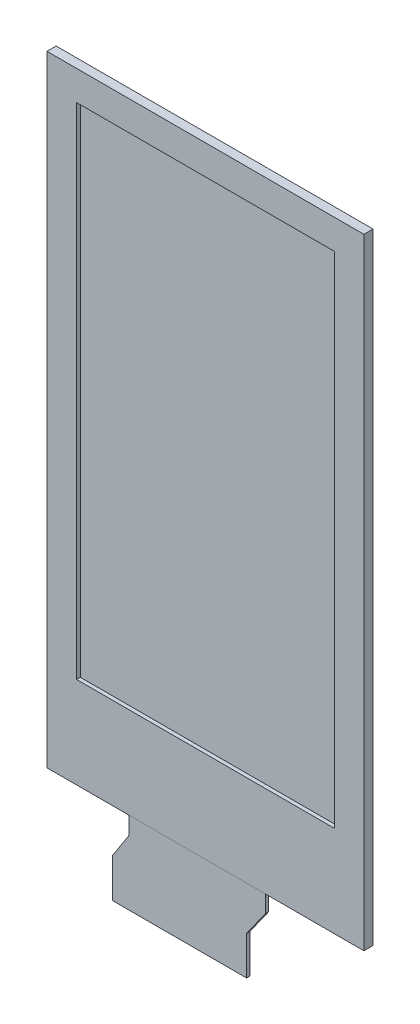
SolidWorks part; units mm, degrees
ref_plane "Front Plane" through (0, 0, 0) normal (0, 0, 1) x (1, 0, 0)
ref_plane "Top Plane" through (0, 0, 0) normal (0, 1, 0) x (1, 0, 0)
ref_plane "Right Plane" through (0, 0, 0) normal (1, 0, 0) x (0, 0, -1)
sketch "main_features_sketch" plane through (0, 0, 0) normal (0, 0, 1) x (1, 0, 0)
  line L0 (-7.152, -31.75) -> (-7.152, -33.4061)
  line L1 (12, 23.25) -> (-12, 23.25)
  line L2 (12, 23.25) -> (12, -23.25)
  line L3 (12, -23.25) -> (-12, -23.25)
  line L4 (-12, 23.25) -> (-12, -23.25)
  line L5 (0, -23.25) -> (0, 23.25) construction
  line L6 (12, 0) -> (-12, 0) construction
  line L7 (14.748, 26) -> (-14.752, 26)
  line L8 (14.748, 26) -> (14.748, -31.75)
  line L9 (14.748, -31.75) -> (-14.752, -31.75)
  line L10 (-14.752, 26) -> (-14.752, -31.75)
  line L11 (-0.002, -31.75) -> (-0.002, 26) construction
  line L12 (14.748, -2.875) -> (-14.752, -2.875) construction
  line L13 (-7.152, -33.4061) -> (-8.722, -35.849)
  line L14 (-8.722, -35.849) -> (-8.722, -39.45)
  line L15 (-8.722, -39.45) -> (3.778, -39.45)
  line L16 (3.778, -39.45) -> (3.778, -35.849)
  line L17 (3.778, -35.849) -> (5.5182, -33.4061)
  line L18 (5.5182, -33.4061) -> (5.5182, -31.75)
  point P0 (0, 0)
  point P4 (-0.002, -2.875)
  point P10 (-8.722, -38.25)
  point P17 (-7.152, -34.4199)
  point P18 (0, 0)
  point P19 (5.4619, -33.1245)
  point P20 (0, 0)
  point P21 (0, 0)
  point P22 (0, 0)
  point P23 (-7.152, -34.3073)
  dimension "D1" = 24
  dimension "D2" = 29.5
  dimension "D3" = 46.5
  dimension "D4" = 57.75
  dimension "D5" = 12.5
  dimension "D6" = 6.03
  dimension "D7" = 2.748
  dimension "D8" = 2.75
  dimension "D9" = 4.099
  dimension "D10" = 1.57
  dimension "D11" = 7.7
extrude "display" add sketch "main_features_sketch" along normal blind 0.5 contours L1 L4 L3 L2 region at (0, 0, 0)
extrude "bezel" add sketch "Sketch1<3>" along normal blind 0.85 separate body contours L7 L10 L9 L8 L4 L1 L2 L3 region at (-10.952, -31.1015, 0)
sketch "Sketch1<3>" plane through (0, 0, 0) normal (0, 0, 1) x (1, 0, 0) same geometry as "main_features_sketch"
extrude "cable" add sketch "Sketch1<4>" along normal blind 0.3 from offset 0.5 separate body contours L17 L18 L9 L0 L13 L14 L15 L16 region at (-1.8494, -35.5882, 0)
sketch "Sketch1<4>" plane through (0, 0, 0) normal (0, 0, 1) x (1, 0, 0) same geometry as "main_features_sketch"
